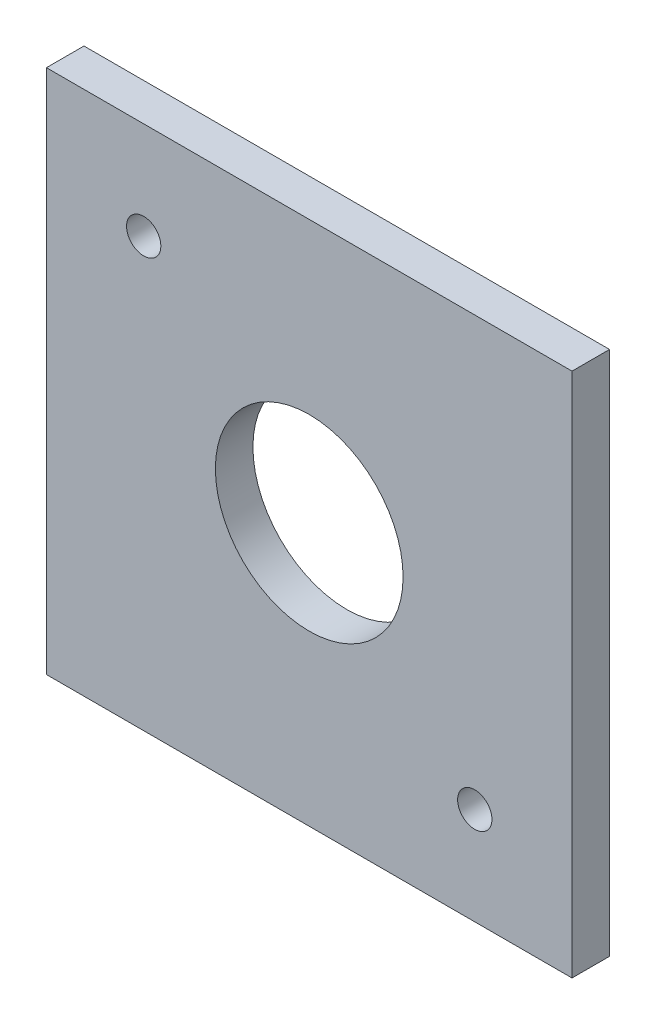
SolidWorks part; units mm, degrees
ref_plane "Front" through (0, 0, 0) normal (0, 0, 1) x (1, 0, 0)
ref_plane "Top" through (0, 0, 0) normal (0, 1, 0) x (1, 0, 0)
ref_plane "Right" through (0, 0, 0) normal (1, 0, 0) x (0, 0, -1)
sketch "Sketch1" plane through (0, 0, 0) normal (0, 0, 1) x (1, 0, 0)
  line L1 (-22.225, -22.225) -> (22.225, -22.225)
  line L2 (-22.225, -22.225) -> (-22.225, 22.225)
  line L3 (-22.225, 22.225) -> (22.225, 22.225)
  line L4 (22.225, -22.225) -> (22.225, 22.225)
  line L5 (-22.225, -22.225) -> (22.225, 22.225) construction
  line L6 (-22.225, 22.225) -> (22.225, -22.225) construction
  point P0 (0, 0)
  dimension "D1" = 44.45
extrude "Boss-Extrude1" add sketch "Sketch1" along normal blind 3.175
sketch "Sketch4" plane through (0, 0, 3.175) normal (0, 0, 1) x (1, 0, 0)
  line L0 (-14, 14) -> (14, 14) construction
  line L1 (14, 14) -> (14, -14) construction
  line L3 (14, -14) -> (-14, -14) construction
  line L4 (-14, -14) -> (-14, 14) construction
  line L6 (0, 14) -> (0, 22.225) construction
  line L7 (22.225, 22.225) -> (-22.225, 22.225) construction
  line L9 (14, 0) -> (22.225, 0) construction
  line L10 (22.225, -22.225) -> (22.225, 22.225) construction
  point P0 (-14, 14)
  point P2 (14, -14)
  dimension "D1" = 28
hole_wizard "M2.5 Clearance Hole1" positions "Sketch4" profile "Sketch3" hole size "M2.5" standard "ANSI Metric" end condition through all
sketch "Sketch3" plane through (-14, 14, 3.175) normal (1, 0, 0) x (0, -1, 0)
  line L0 (0, 0) -> (0, 3.175)
  line L1 (0, 3.175) -> (1.45, 3.175)
  line L2 (1.45, 3.175) -> (1.45, 0)
  line L5 (1.45, 0) -> (0, 0)
  line L11 (0, -6.35) -> (0, 107.95) construction
  dimension "Thru Hole Dia." = 2.9
  dimension "Thru Hole Depth" = 3.175
sketch "Sketch5" plane through (0, 0, 3.175) normal (0, 0, 1) x (1, 0, 0)
  circle A0 centre (0, 0) radius 7.9375
  dimension "D1" = 15.875
extrude "Cut-Extrude1" cut sketch "Sketch5" against normal through all
